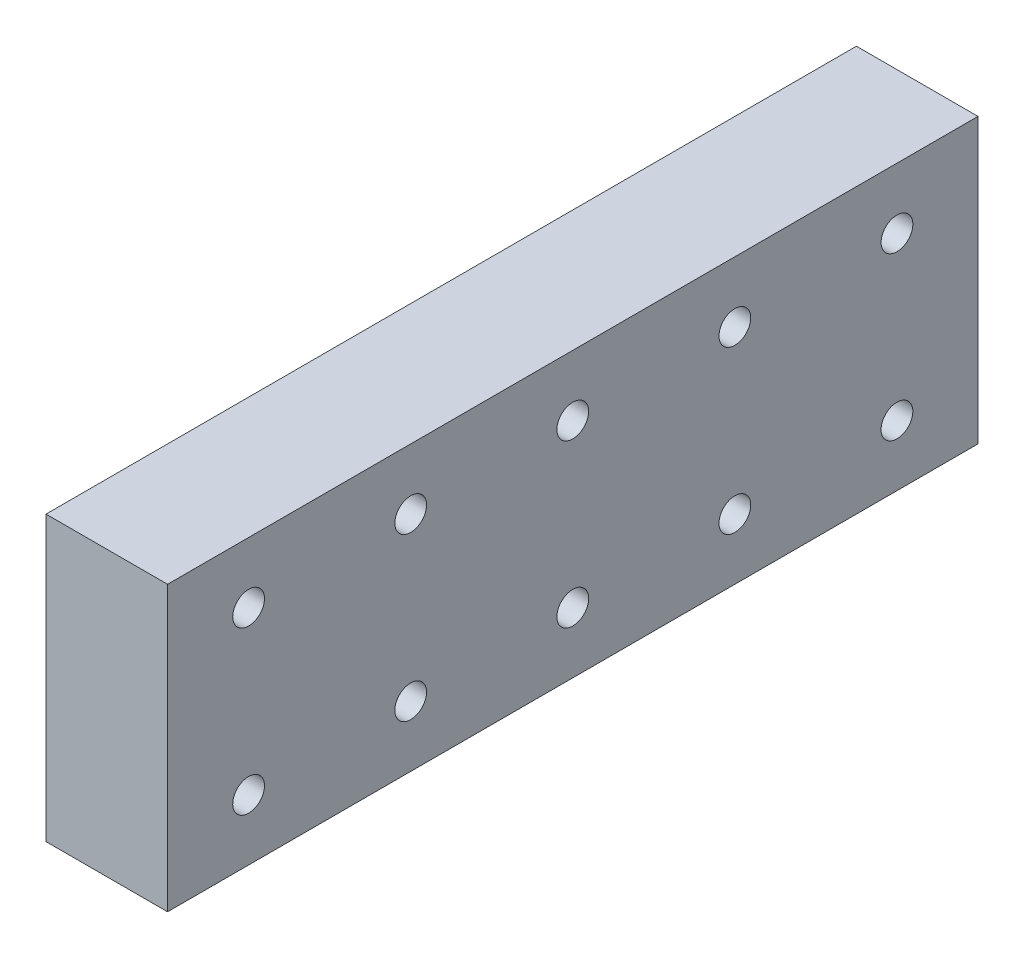
SolidWorks part; units mm, degrees
material "PET"
ref_plane "Front Plane" through (0, 0, 0) normal (0, 0, 1) x (1, 0, 0)
ref_plane "Top Plane" through (0, 0, 0) normal (0, 1, 0) x (1, 0, 0)
ref_plane "Right Plane" through (0, 0, 0) normal (1, 0, 0) x (0, 0, -1)
sketch "Sketch1" plane through (0, 0, 0) normal (0, 0, 1) x (1, 0, 0)
  line L1 (0, 0) -> (19.05, 0)
  line L2 (0, 0) -> (0, 44.45)
  line L3 (0, 44.45) -> (19.05, 44.45)
  line L4 (19.05, 0) -> (19.05, 44.45)
  dimension "D1" = 44.45
  dimension "D2" = 19.05
extrude "Boss-Extrude1" add sketch "Sketch1" along normal blind 127
sketch "Sketch2" plane through (19.05, 0, 0) normal (1, 0, 0) x (0, 0, -1)
  line L0 (-127, 0) -> (0, 0) construction
  line L1 (-127, 0) -> (-127, 44.45) construction
  circle A0 centre (-114.3, 9.525) radius 2.4892
  circle A1 centre (-88.9, 9.525) radius 2.4892
  circle A2 centre (-63.5, 9.525) radius 2.4892
  circle A3 centre (-114.3, 34.925) radius 2.4892
  circle A4 centre (-88.9, 34.925) radius 2.4892
  circle A5 centre (-63.5, 34.925) radius 2.4892
  circle A6 centre (-38.1, 9.525) radius 2.4892
  circle A7 centre (-12.7, 9.525) radius 2.4892
  circle A12 centre (-38.1, 34.925) radius 2.4892
  circle A13 centre (-12.7, 34.925) radius 2.4892
  dimension "D1" = 4.9784
  dimension "D2" = 9.525
  dimension "D3" = 12.7
  dimension "D4" = 5
  dimension "D5" = 2
extrude "Cut-Extrude1" cut sketch "Sketch2" against normal through all
